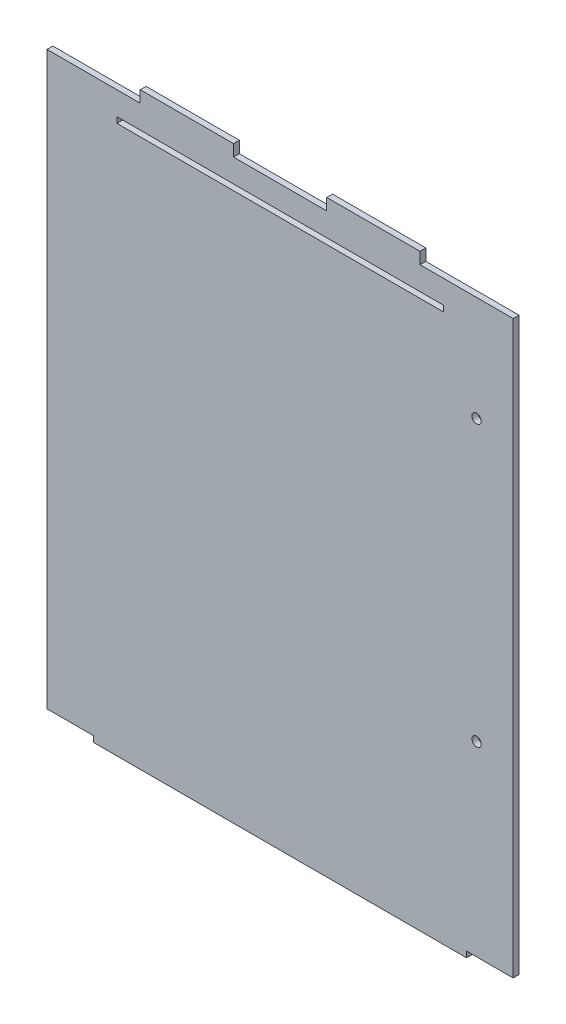
SolidWorks part; units mm, degrees
ref_plane "Front Plane" through (0, 0, 0) normal (0, 0, 1) x (1, 0, 0)
ref_plane "Top Plane" through (0, 0, 0) normal (0, 1, 0) x (1, 0, 0)
ref_plane "Right Plane" through (0, 0, 0) normal (1, 0, 0) x (0, 0, -1)
sketch "Sketch1" plane through (0, 0, 0) normal (0, 0, 1) x (1, 0, 0)
  line L0 (0, -9.525) -> (25.4, -9.525)
  line L1 (25.4, -12.7) -> (228.6, -12.7)
  line L2 (0, -9.525) -> (0, 301.625)
  line L3 (50.8, 307.975) -> (101.6, 307.975)
  line L4 (254, -9.525) -> (254, 301.625)
  line L5 (25.4, -9.525) -> (25.4, -12.7)
  line L6 (25.4, -12.7) -> (228.6, -12.7)
  line L7 (0, 301.625) -> (50.8, 301.625)
  line L8 (50.8, 301.625) -> (50.8, 307.975)
  line L9 (50.8, 307.975) -> (101.6, 307.975)
  line L10 (101.6, 307.975) -> (101.6, 301.625)
  line L11 (101.6, 301.625) -> (152.4, 301.625)
  line L12 (152.4, 301.625) -> (152.4, 307.975)
  line L13 (152.4, 307.975) -> (203.2, 307.975)
  line L14 (203.2, 307.975) -> (203.2, 301.625)
  line L15 (203.2, 301.625) -> (254, 301.625)
  line L16 (152.4, 307.975) -> (203.2, 307.975)
  line L17 (228.6, -12.7) -> (228.6, -9.525)
  line L18 (228.6, -9.525) -> (254, -9.525)
  line L20 (38.1, 288.925) -> (215.9, 288.925)
  line L21 (38.1, 288.925) -> (38.1, 285.75)
  line L22 (38.1, 285.75) -> (215.9, 285.75)
  line L23 (215.9, 288.925) -> (215.9, 285.75)
  dimension "D1" = 320.675
  dimension "D2" = 3.175
  dimension "D3" = 6.35
  dimension "D4" = 50.8
  dimension "D5" = 50.8
  dimension "D6" = 50.8
  dimension "D7" = 50.8
  dimension "D8" = 50.8
  dimension "D9" = 3.175
  dimension "D10" = 25.4
  dimension "D11" = 25.4
  dimension "D12" = 3.175
  dimension "D13" = 177.8
  dimension "D14" = 38.1
  dimension "D15" = 12.7
extrude "Boss-Extrude1" add sketch "Sketch1" along normal blind 3.175 contours L17 L18 L4 L15 L14 L13 L12 L11 L10 L3 L8 L7 L2 L0 L5 L1 L20 L23 L22 L21 region at (127, 145.0628, 0)
sketch "Sketch2" plane through (0, 0, 0) normal (0, 0, -1) x (-1, 0, 0)
  line L0 (-228.6, -9.525) -> (-254, -9.525) construction
  circle A0 centre (-234.0633, 244.475) radius 2.54
  circle A1 centre (-234.0633, 92.075) radius 2.54
  dimension "D1" = 5.08
  dimension "D2" = 101.6
  dimension "D3" = 152.4
extrude "Cut-Extrude1" cut sketch "Sketch2" against normal through all
